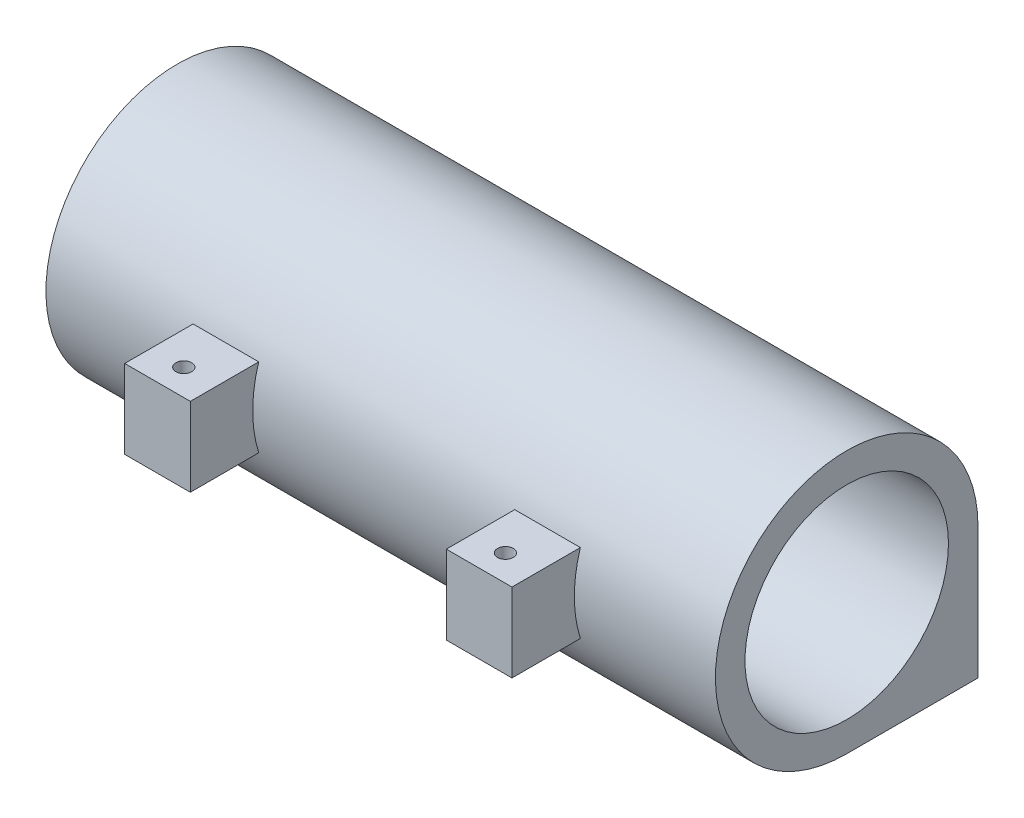
SolidWorks part; units mm, degrees
ref_plane "Front Plane" through (0, 0, 0) normal (0, 0, 1) x (1, 0, 0)
ref_plane "Top Plane" through (0, 0, 0) normal (0, 1, 0) x (1, 0, 0)
ref_plane "Right Plane" through (0, 0, 0) normal (1, 0, 0) x (0, 0, -1)
sketch "Sketch1" plane through (0, 0, 0) normal (1, 0, 0) x (0, 0, -1)
  line L1 (-20.9452, 21.1459) -> (13.0548, 21.1459)
  line L2 (-20.9452, 21.1459) -> (-20.9452, -8.8541)
  line L3 (-20.9452, -8.8541) -> (13.0548, -8.8541)
  line L4 (13.0548, 21.1459) -> (13.0548, -8.8541)
  dimension "D1" = 34
  dimension "D2" = 30
extrude "Boss-Extrude2" add sketch "Sketch1" along normal blind 51
sketch "Sketch3" plane through (0, 0, -13.0548) normal (0, 0, -1) x (-1, 0, 0)
  line L0 (-51, -8.8541) -> (0, -8.8541) construction
  line L1 (-51, -8.8541) -> (-51, 21.1459) construction
  circle A0 centre (-25.5, -1.3541) radius 2.55
  point P2 (-25.5, -8.8541)
  dimension "D1" = 7.5
  dimension "D2" = 5.1
  dimension "D3" = 25.5
extrude "Cut-Extrude3" cut sketch "Sketch3" against normal blind 10
sketch "Sketch5" plane through (51, 0, 0) normal (1, 0, 0) x (0, 0, -1)
  line L0 (13.0548, -8.8541) -> (13.0548, 21.1459) construction
  line L1 (-20.9452, -8.8541) -> (13.0548, -8.8541) construction
  circle A0 centre (-3.9452, 1.1459) radius 7.75
  dimension "D1" = 17
  dimension "D2" = 10
extrude "Cut-Extrude4" cut sketch "Sketch5" against normal blind 51
sketch "Sketch6" plane through (51, 0, 0) normal (1, 0, 0) x (0, 0, -1)
  line L0 (-20.9452, -8.8541) -> (13.0548, -8.8541) construction
  line L1 (13.0548, 21.1459) -> (6.0548, 21.1459)
  line L2 (13.0548, 21.1459) -> (13.0548, -8.8541)
  line L3 (13.0548, -8.8541) -> (6.0548, -8.8541)
  line L4 (6.0548, 21.1459) -> (6.0548, -8.8541)
  dimension "D1" = 7
extrude "Cut-Extrude6" cut sketch "Sketch6" against normal blind 51
sketch "Sketch7" plane through (51, 0, 0) normal (1, 0, 0) x (0, 0, -1)
  line L1 (-3.9452, -8.8541) -> (-20.9452, -8.8541)
  line L2 (6.0548, 1.1459) -> (6.0548, 21.1459)
  line L3 (6.0548, 21.1459) -> (-20.9452, 21.1459)
  line L4 (-20.9452, -8.8541) -> (-20.9452, 21.1459)
  arc A0 (6.0548, 1.1459) -> (-3.9452, -8.8541) centre (-3.9452, 1.1459) ccw
extrude "Cut-Extrude7" cut sketch "Sketch7" against normal blind 51
sketch "Sketch8" plane through (0, 0, -3.0548) normal (0, 0, -1) x (-1, 0, 0)
  line L2 (-21.75, -2.1801) -> (-21.75, -4.9041)
  line L3 (-21.75, -4.9041) -> (-29.25, -4.9041)
  line L4 (-29.25, -2.1801) -> (-29.25, -4.9041)
  line L6 (-29.25, -2.1801) -> (-29.25, 2.1959)
  line L7 (-29.25, 2.1959) -> (-21.75, 2.1959)
  line L8 (-21.75, -2.1801) -> (-21.75, 2.1959)
  arc A0 (-27.9125, -2.1801) -> (-23.0875, -2.1801) centre (-25.5, -1.3541) ccw construction
  arc A1 (-24.9975, 1.1459) -> (-26.0025, 1.1459) centre (-25.5, -1.3541) ccw construction
  point P4 (-25.5, -3.9041)
  point P8 (-25.5, -3.9041)
  point P11 (-25.5, 1.1959)
  dimension "D1" = 7.5
  dimension "D2" = 3.75
  dimension "D3" = 1
  dimension "D4" = 1
extrude "Cut-Extrude9" cut sketch "Sketch8" against normal blind 1.5 and the other way blind 1.5
sketch "Sketch10" plane through (51, 0, 0) normal (1, 0, 0) x (0, 0, -1)
  line L1 (-17.6952, 1.1459) -> (-17.6952, 4.1459)
  line L2 (-17.6952, 4.1459) -> (-11.6952, 4.1459)
  line L3 (-11.6952, 4.1459) -> (-11.6952, 1.1459)
  line L4 (-11.6952, -1.8541) -> (-17.6952, -1.8541)
  line L5 (-17.6952, -1.8541) -> (-17.6952, 1.1459)
  line L6 (-11.6952, -1.8541) -> (-11.6952, 1.1459)
  circle A0 centre (-3.9452, 1.1459) radius 7.75 construction
  dimension "D1" = 3
  dimension "D2" = 3
  dimension "D3" = 6
extrude "Boss-Extrude5" add sketch "Sketch10" against normal blind 51
sketch "Sketch11" plane through (51, 0, 0) normal (1, 0, 0) x (0, 0, -1)
  line L0 (-13.4846, -1.8541) -> (-17.6952, -1.8541)
  line L1 (-17.6952, -1.8541) -> (-17.6952, 4.1459)
  line L2 (-17.6952, 4.1459) -> (-13.4846, 4.1459)
  arc A0 (-13.4846, 4.1459) -> (-13.4846, -1.8541) centre (-3.9452, 1.1459) ccw
extrude "Cut-Extrude10" cut sketch "Sketch11" against normal blind 13
sketch "Sketch12" plane through (0, 0, 0) normal (-1, 0, 0) x (0, 0, 1)
  line L0 (13.4846, -1.8541) -> (17.6952, -1.8541)
  line L1 (17.6952, -1.8541) -> (17.6952, 4.1459)
  line L2 (17.6952, 4.1459) -> (13.4846, 4.1459)
  arc A0 (13.4846, -1.8541) -> (13.4846, 4.1459) centre (3.9452, 1.1459) ccw
extrude "Cut-Extrude11" cut sketch "Sketch12" against normal blind 13
sketch "Sketch13" plane through (0, 0, 17.6952) normal (0, 0, 1) x (1, 0, 0)
  line L0 (13, -1.8541) -> (13, 4.1459) construction
  line L1 (24.5, -1.8541) -> (26.5, -1.8541)
  line L2 (24.5, -1.8541) -> (24.5, 4.1459)
  line L3 (24.5, 4.1459) -> (26.5, 4.1459)
  line L4 (26.5, -1.8541) -> (26.5, 4.1459)
  line L5 (38, 4.1459) -> (38, -1.8541) construction
  line L6 (13, 4.1459) -> (38, 4.1459) construction
  line L7 (13, -1.8541) -> (38, -1.8541) construction
  dimension "D1" = 2
  dimension "D2" = 11.5
  dimension "D3" = 11.5
  dimension "D4" = 0
  dimension "D5" = 0
extrude "Cut-Extrude12" cut sketch "Sketch13" against normal blind 2
sketch "Sketch15" plane through (24.5, 0, 0) normal (1, 0, 0) x (0, 0, -1)
  line L0 (-17.6952, 4.1459) -> (-17.6952, -1.8541)
  line L1 (-17.6952, -1.8541) -> (-13.4846, -1.8541)
  line L2 (-13.4846, -1.8541) -> (-17.6952, -1.8541) construction
  line L4 (-13.4846, 4.1459) -> (-17.6952, 4.1459)
  arc A0 (-13.4846, 4.1459) -> (-13.4846, -1.8541) centre (-3.9452, 1.1459) ccw
extrude "Cut-Extrude13" cut sketch "Sketch15" against normal blind 11 and the other way blind 13
sketch "Sketch17" plane through (38, 0, 0) normal (1, 0, 0) x (0, 0, -1)
  line L0 (-13.4846, 4.1459) -> (-17.6952, 4.1459)
  line L1 (-17.6952, 4.1459) -> (-17.6952, -1.8541)
  line L2 (-17.6952, -1.8541) -> (-13.4846, -1.8541)
  arc A0 (-13.4846, 4.1459) -> (-13.4846, -1.8541) centre (-3.9452, 1.1459) ccw
extrude "Boss-Extrude6" add sketch "Sketch17" along normal blind 2.25
sketch "Sketch19" plane through (13, 0, 0) normal (-1, 0, 0) x (0, 0, 1)
  line L0 (13.4846, 4.1459) -> (17.6952, 4.1459)
  line L1 (17.6952, 4.1459) -> (17.6952, -1.8541)
  line L2 (17.6952, -1.8541) -> (13.4846, -1.8541)
  arc A0 (13.4846, -1.8541) -> (13.4846, 4.1459) centre (3.9452, 1.1459) ccw
extrude "Boss-Extrude7" add sketch "Sketch19" along normal blind 2.25
sketch "Sketch20" plane through (13.5, 0, 0) normal (1, 0, 0) x (0, 0, -1)
  line L0 (-17.6952, -1.8541) -> (-17.6952, 4.1459)
  line L1 (-17.6952, 4.1459) -> (-13.4846, 4.1459)
  line L3 (-13.4846, -1.8541) -> (-17.6952, -1.8541)
  arc A0 (-13.4846, 4.1459) -> (-13.4846, -1.8541) centre (-3.9452, 1.1459) ccw
extrude "Boss-Extrude8" add sketch "Sketch20" along normal blind 2.25
sketch "Sketch21" plane through (37.5, 0, 0) normal (-1, 0, 0) x (0, 0, 1)
  line L0 (13.4846, 4.1459) -> (17.6952, 4.1459)
  line L1 (17.6952, 4.1459) -> (17.6952, -1.8541)
  line L2 (17.6952, -1.8541) -> (13.4846, -1.8541)
  line L3 (13.4846, -1.8541) -> (17.6952, -1.8541) construction
  arc A0 (13.4846, -1.8541) -> (13.4846, 4.1459) centre (3.9452, 1.1459) ccw
extrude "Boss-Extrude9" add sketch "Sketch21" along normal blind 2.25
sketch "Sketch22" plane through (0, 0, 17.6952) normal (0, 0, 1) x (1, 0, 0)
  line L1 (35.25, -1.8541) -> (40.25, -1.8541)
  line L2 (35.25, -1.8541) -> (35.25, 4.1459)
  line L3 (35.25, 4.1459) -> (40.25, 4.1459)
  line L4 (40.25, -1.8541) -> (40.25, 4.1459)
extrude "Boss-Extrude10" add sketch "Sketch22" along normal blind 1
sketch "Sketch24" plane through (0, 0, 17.6952) normal (0, 0, 1) x (1, 0, 0)
  line L1 (10.75, -1.8541) -> (15.75, -1.8541)
  line L2 (10.75, -1.8541) -> (10.75, 4.1459)
  line L3 (10.75, 4.1459) -> (15.75, 4.1459)
  line L4 (15.75, -1.8541) -> (15.75, 4.1459)
extrude "Boss-Extrude11" add sketch "Sketch24" along normal blind 1
sketch "Sketch25" plane through (0, 4.1459, 0) normal (0, 1, 0) x (1, 0, 0)
  line L0 (10.75, -18.6952) -> (10.75, -13.4846) construction
  line L1 (15.75, -13.4846) -> (15.75, -18.6952) construction
  line L2 (15.75, -18.6952) -> (10.75, -18.6952) construction
  line L3 (10.75, -13.4846) -> (15.75, -13.4846) construction
  line L4 (40.25, -13.4846) -> (40.25, -18.6952) construction
  circle A0 centre (13.25, -16.6952) radius 0.6
  circle A1 centre (37.75, -16.6952) radius 0.6
  dimension "D1" = 2.5
  dimension "D5" = 2.5
  dimension "D2" = 2.5
  dimension "D3" = 2
  dimension "D4" = 3.2106
extrude "Cut-Extrude14" cut sketch "Sketch25" against normal blind 20
